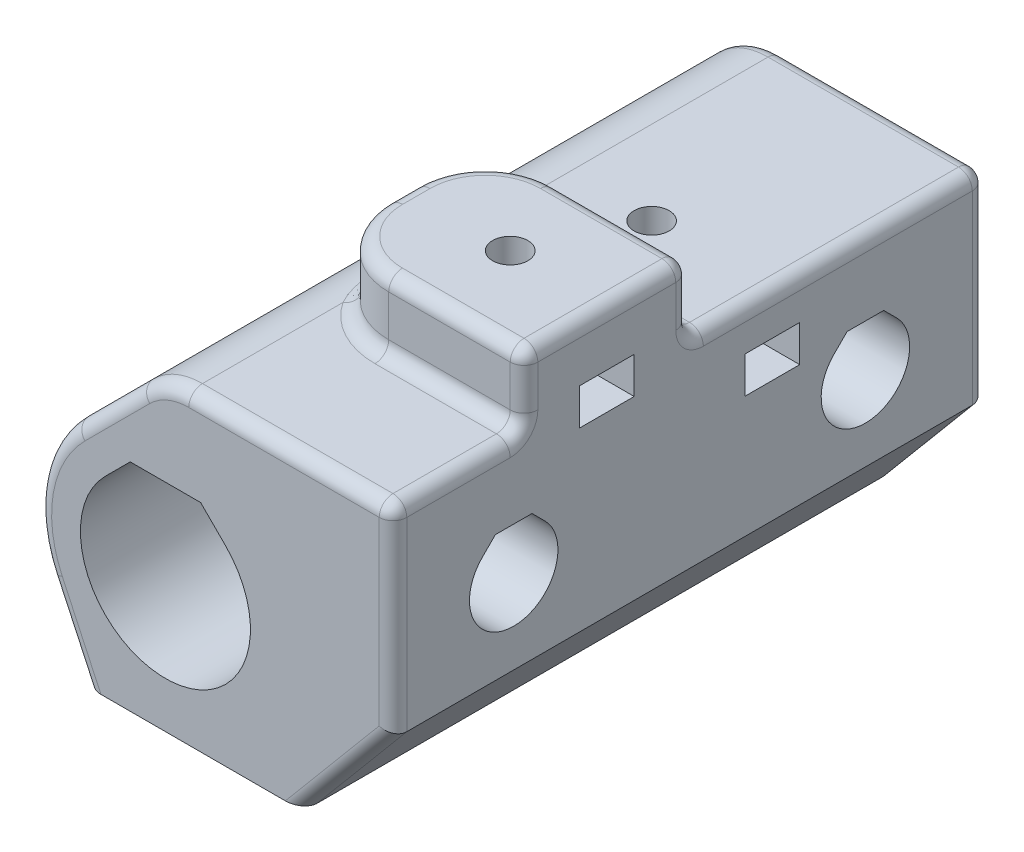
SolidWorks part; units mm, degrees
ref_plane "Front Plane" through (0, 0, 0) normal (0, 0, 1) x (1, 0, 0)
ref_plane "Top Plane" through (0, 0, 0) normal (0, 1, 0) x (1, 0, 0)
ref_plane "Right Plane" through (0, 0, 0) normal (1, 0, 0) x (0, 0, -1)
sketch "Sketch1" plane through (0, 0, 0) normal (0, 0, 1) x (1, 0, 0)
  line L0 (-16.7667, -7.8184) -> (-11.5526, -19)
  line L1 (-13.0815, 13.0815) -> (-3.6919, 22.4711)
  line L2 (3.3792, 25.4) -> (33, 25.4)
  line L3 (33, 25.4) -> (33, -3.5072)
  line L4 (20, -19) -> (-11.5526, -19)
  line L5 (20, -19) -> (33, -3.5072)
  line L6 (8.7151, 8.7151) -> (5.1052, 12.325)
  line L7 (5.1052, 12.325) -> (-5.1052, 12.325)
  line L8 (-5.1052, 12.325) -> (-8.7151, 8.7151)
  arc A0 (-8.7151, 8.7151) -> (8.7151, 8.7151) centre (0, 0) ccw
  arc A1 (3.3792, 25.4) -> (-3.6919, 22.4711) centre (3.3792, 15.4) ccw
  arc A2 (-13.0815, 13.0815) -> (-16.7667, -7.8184) centre (0, 0) ccw
  dimension "D2" = 115
  dimension "D4" = 19
  dimension "D3" = 110
  dimension "D5" = 130
  dimension "D11" = 20
  dimension "D16" = 18.5
  dimension "D14" = 33
  dimension "D6" = 24.65
  dimension "D10" = 10
  dimension "D7" = 25.4
  dimension "D8" = 135
  dimension "D9" = 135
extrude "Boss-Extrude1" add sketch "Sketch1" along normal mid plane 86
sketch "Sketch10" plane through (33, 0, 0) normal (1, 0, 0) x (0, 0, -1)
  line L0 (-43, 25.4) -> (43, 25.4) construction
  line L2 (0, 25.4) -> (0, -19) construction
  line L3 (-43, -19) -> (43, -19) construction
  line L4 (-30.035, 12.935) -> (-28.1566, 14.8135)
  line L5 (-28.1566, 14.8135) -> (-22.8434, 14.8135)
  line L6 (-22.8434, 14.8135) -> (-20.965, 12.935)
  line L7 (22.8434, 14.8135) -> (20.965, 12.935)
  line L8 (28.1566, 14.8135) -> (22.8434, 14.8135)
  line L9 (30.035, 12.935) -> (28.1566, 14.8135)
  arc A0 (-30.035, 12.935) -> (-20.965, 12.935) centre (-25.5, 8.4) ccw
  arc A1 (30.035, 12.935) -> (20.965, 12.935) centre (25.5, 8.4) cw
  dimension "D1" = 12.827
  dimension "D2" = 17
  dimension "D3" = 25.5
  dimension "D4" = 135
  dimension "D5" = 135
ref_axis "Axis1" through (0, 0, 43) along (0, 0, -1)
ref_plane "Plane1" through (0, 0, 0) normal (1, 0, 0) x (0, 0, -1)
ref_plane "Plane2" through (15.25, 0, 0) normal (1, 0, 0) x (0, 0, -1)
extrude "Cut-Extrude9" cut sketch "Sketch10" against normal up to surface (17.75 mm away) up to plane "Plane2"
sketch "Sketch11" plane through (0, 25.4, 0) normal (0, 1, 0) x (1, 0, 0)
  line L0 (33, 0) -> (-18.5, 0) construction
  line L1 (33, -43) -> (33, 43) construction
  line L2 (-18.5, 43) -> (-18.5, -43) construction
  line L5 (0, -43) -> (0, 43) construction
  circle A0 centre (15.5, 12) radius 2.55
  circle A1 centre (15.5, 12) radius 11 construction
  dimension "D1" = 15.5
  dimension "D2" = 22
  dimension "D3" = 12
  dimension "D4" = 5.1
extrude "Cut-Extrude10" cut sketch "Sketch11" against normal blind 15
sketch "Sketch12" plane through (0, 25.4, 0) normal (0, 1, 0) x (1, 0, 0)
  line L0 (13.3792, 0) -> (33, 0)
  line L2 (33, -43) -> (33, 43) construction
  line L3 (33, 0) -> (33, -24)
  line L4 (13.3792, -24) -> (33, -24)
  line L5 (3.3792, -43) -> (3.3792, 43) construction
  line L6 (3.3792, -14) -> (3.3792, -10)
  arc A0 (13.3792, -24) -> (3.3792, -14) centre (13.3792, -14) cw
  arc A1 (3.3792, -10) -> (13.3792, 0) centre (13.3792, -10) cw
  dimension "D2" = 10
  dimension "D1" = 24
extrude "Boss-Extrude2" add sketch "Sketch12" along normal blind 10
sketch "Sketch13" plane through (0, 35.4, 0) normal (0, 1, 0) x (1, 0, 0)
  line L0 (33, 0) -> (13.3792, 0) construction
  line L3 (0, -43) -> (0, 43) construction
  circle A0 centre (19, -12) radius 2.55
  dimension "D1" = 5.1
  dimension "D2" = 12
  dimension "D3" = 19
extrude "Cut-Extrude11" cut sketch "Sketch13" against normal blind 19
ref_plane "Plane3" through (0, 27.4, 0) normal (0, 1, 0) x (1, 0, 0)
sketch "Sketch14" plane through (0, 27.4, 0) normal (0, 1, 0) x (1, 0, 0)
  line L0 (19, -12) -> (33, -12) construction
  line L1 (33, -24) -> (33, 0) construction
  line L2 (33, -15.975) -> (33, -8.025)
  line L3 (14.4101, -12) -> (16.705, -15.975)
  line L4 (16.705, -15.975) -> (33, -15.975)
  line L7 (33, -8.025) -> (16.705, -8.025)
  line L8 (16.705, -8.025) -> (14.4101, -12)
  line L9 (23.2868, -12.525) -> (24.456, -10.5) [skipped]
  line L10 (23.2868, -11.475) -> (22.1177, -9.45) [skipped]
  circle A0 centre (19, -12) radius 3.975 construction
  dimension "D1" = 7.95
extrude "Cut-Extrude12" cut sketch "Sketch14" against normal blind 5.3
ref_plane "Plane4" through (0, 19.4, 0) normal (0, 1, 0) x (1, 0, 0)
sketch "Sketch15" plane through (0, 19.4, 0) normal (0, 1, 0) x (1, 0, 0)
  line L1 (10.9101, 12) -> (13.205, 8.025)
  line L2 (13.205, 8.025) -> (33, 8.025)
  line L3 (33, 8.025) -> (33, 15.975)
  line L4 (33, 15.975) -> (33.0043, 15.9616)
  line L5 (33, 15.975) -> (13.205, 15.975)
  line L6 (13.205, 15.975) -> (10.9101, 12)
  line L7 (10.7084, 12) -> (33, 12) construction
  line L8 (33, 0) -> (33, 43) construction
  line L10 (20.1792, 11.8454) -> (17.841, 15.8953) [skipped]
  line L11 (17.7057, 7.8704) -> (20.0439, 11.9203) [skipped]
  circle A0 centre (15.5, 12) radius 3.975 construction
  dimension "D1" = 7.95
extrude "Cut-Extrude13" cut sketch "Sketch15" against normal blind 5.3 contours L5 L6 L1 L2 L3 region at (22.5183, 19.4, -12)
sketch "Sketch16" plane through (0, 19.4, 0) normal (0, -1, 0) x (1, 0, 0)
  circle A0 centre (15.5, -12) radius 2.55 construction
  circle A1 centre (15.5, -12) radius 2.55
extrude "Boss-Extrude3" add sketch "Sketch16" against normal blind 0.22
sketch "Sketch17" plane through (0, 27.4, 0) normal (0, -1, 0) x (1, 0, 0)
  line L5 (14.4101, 12) -> (16.705, 8.025)
  line L6 (16.705, 8.025) -> (33, 8.025)
  line L7 (33, 8.025) -> (33, 15.975)
  line L8 (33, 15.975) -> (16.705, 15.975)
  line L9 (16.705, 15.975) -> (14.4101, 12)
  line L10 (14.4101, 12) -> (16.705, 8.025)
  line L11 (16.705, 8.025) -> (33, 8.025)
  line L12 (33, 8.025) -> (33, 15.975)
  line L13 (33, 15.975) -> (16.705, 15.975)
  line L14 (16.705, 15.975) -> (14.4101, 12)
  dimension "D1" = 0
extrude "Boss-Extrude4" add sketch "Sketch17" against normal blind 0.22
fillet "Fillet10" radius 2 29 edges at (33, 25.4, -21.5) (-14.1597, -13.4092, 43) (-18.2189, 3.2125, 43) (-14.1597, -13.4092, -43) (-18.2189, 3.2125, -43) (33, 30.4, 0) (33, 35.4, 12) (23.1896, 35.4, 0) (-8.3867, 17.7763, 43) (33, 10.9464, 43) (26.5, -11.2536, 43) (26.5, -11.2536, -43) (33, 10.9464, -43) (18.1896, 25.4, -43) (-8.3867, 17.7763, -43) (23.1896, 35.4, 24) (6.3081, 35.4, 21.0711) (3.3792, 35.4, 12) (6.3081, 35.4, 2.9289) (18.1896, 25.4, 43) (-0.4476, 24.6388, 43) (-0.4476, 24.6388, -43) (33, 30.4, 24) (23.1896, 25.4, 0) (6.3081, 25.4, 2.9289) (3.3792, 25.4, 12) (23.1896, 25.4, 24) (33, 25.4, 33.5) (6.3081, 25.4, 21.0711)
